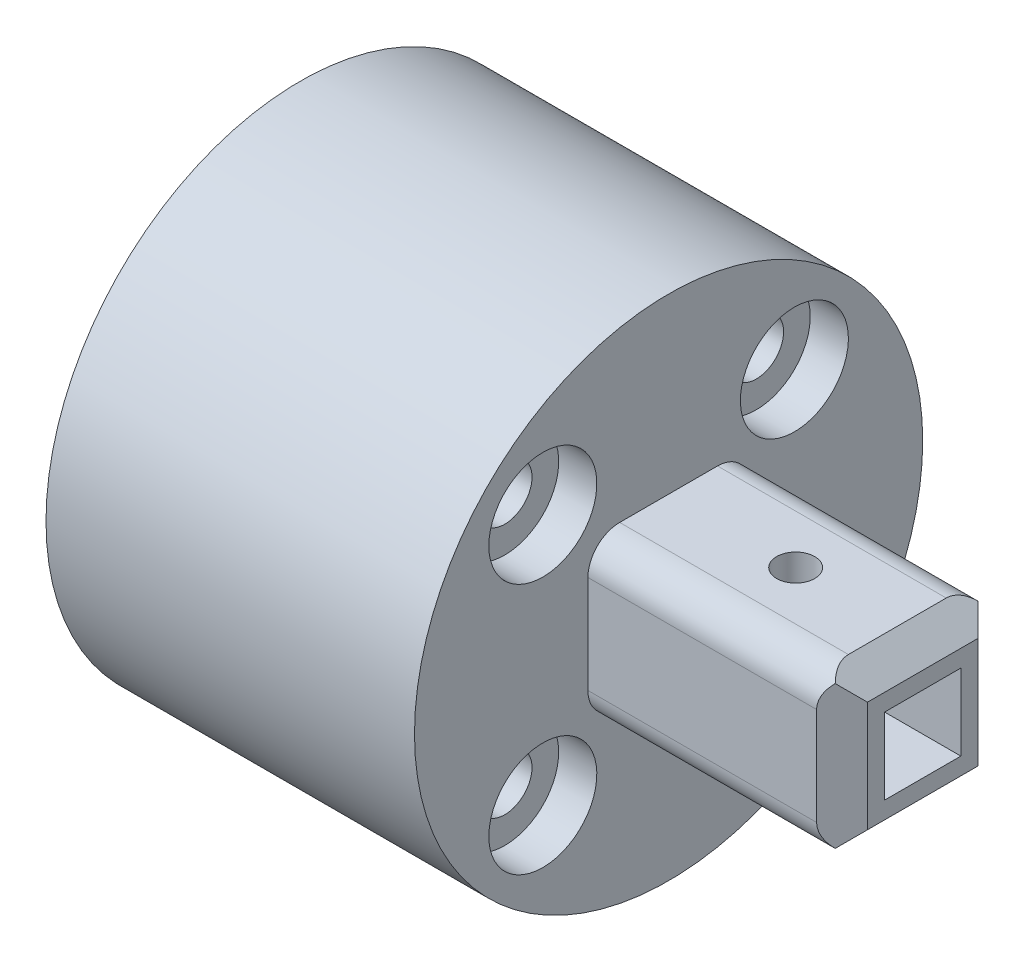
SolidWorks part; units mm, degrees
ref_plane "前视基准面" through (0, 0, 0) normal (0, 0, 1) x (1, 0, 0)
ref_plane "上视基准面" through (0, 0, 0) normal (0, 1, 0) x (1, 0, 0)
ref_plane "右视基准面" through (0, 0, 0) normal (1, 0, 0) x (0, 0, -1)
sketch "草图1" plane through (0, 0, 0) normal (1, 0, 0) x (0, 0, -1)
  circle A0 centre (0, 0) radius 20
  dimension "D1" = 40
extrude "凸台-拉伸1" add sketch "草图1" along normal blind 10
sketch "草图2" plane through (0, 0, 0) normal (-1, 0, 0) x (0, 0, 1)
  line L1 (-7.5, -15.25) -> (7.5, -15.25)
  line L2 (-7.5, -15.25) -> (-7.5, 15.25)
  line L3 (-7.5, 15.25) -> (7.5, 15.25)
  line L4 (7.5, -15.25) -> (7.5, 15.25)
  line L5 (-7.5, -15.25) -> (7.5, 15.25) construction
  line L6 (-7.5, 15.25) -> (7.5, -15.25) construction
  point P0 (0, 0)
  dimension "D1" = 15
  dimension "D2" = 30.5
extrude "切除-拉伸1" cut sketch "草图2" against normal blind 4
sketch "草图3" plane through (4, 0, 0) normal (-1, 0, 0) x (0, 0, 1)
  circle A0 centre (0, 0) radius 8.75
  dimension "D1" = 17.5
extrude "切除-拉伸2" cut sketch "草图3" along normal blind 4
sketch "草图4" plane through (0, 0, 0) normal (-1, 0, 0) x (0, 0, 1)
  line L1 (-9, -16) -> (9, -16)
  line L2 (-9, -16) -> (-9, 16)
  line L3 (-9, 16) -> (9, 16)
  line L4 (9, -16) -> (9, 16)
  line L5 (-9, -16) -> (9, 16) construction
  line L6 (-9, 16) -> (9, -16) construction
  circle A0 centre (0, 0) radius 20
  dimension "D3" = 40
  dimension "D1" = 32
  dimension "D2" = 18
extrude "凸台-拉伸2" add sketch "草图4" along normal blind 19
fillet "圆角1" radius 3 4 edges at (-9.5, -16, -9) (-9.5, -16, 9) (-9.5, 16, -9) (-9.5, 16, 9)
sketch "草图5" plane through (-19, 0, 0) normal (-1, 0, 0) x (0, 0, 1)
  line L0 (-6, -16) -> (6, -16) construction
  line L1 (6, 16) -> (-6, 16) construction
  circle A0 centre (0, -16) radius 2.5
  circle A1 centre (0, 16) radius 2.5
  dimension "D1" = 5
  dimension "D2" = 5
extrude "切除-拉伸3" cut sketch "草图5" against normal blind 20
fillet "圆角2" radius 3 4 edges at (-9.5, -16, -2.5) (-9.5, -16, 2.5) (-9.5, 16, 2.5) (-9.5, 16, -2.5)
sketch "草图6" plane through (10, 0, 0) normal (1, 0, 0) x (0, 0, -1)
  line L0 (0, 0) -> (20, 0) construction
  line L1 (0, 0) -> (18.216, -18.216) construction
  circle A0 centre (0, 0) radius 14 construction
  circle A2 centre (9.8995, -9.8995) radius 2.15
  circle A3 centre (0, 0) radius 14 construction
  circle A4 centre (-9.8995, -9.8995) radius 2.15
  circle A5 centre (0, 0) radius 14 construction
  circle A6 centre (-9.8995, 9.8995) radius 2.15
  circle A7 centre (0, 0) radius 14 construction
  circle A8 centre (9.8995, 9.8995) radius 2.15
  point P21 (0, 0)
  dimension "D1" = 28
  dimension "D3" = 4.3
  dimension "D2" = 45
  dimension "D4" = 4
extrude "切除-拉伸4" cut sketch "草图6" against normal blind 43
fillet "圆角3" radius 1 8 edges at (-9.5, -7.9467, 9) (-9.5, -11.8523, 9) (-9.5, -11.8523, -9) (-9.5, -7.9467, -9) (-9.5, 7.9467, -9) (-9.5, 11.8523, -9) (-9.5, 11.8523, 9) (-9.5, 7.9467, 9)
sketch "草图7" plane through (10, 0, 0) normal (1, 0, 0) x (0, 0, -1)
  circle A0 centre (9.8995, -9.8995) radius 4.25
  dimension "D1" = 8.5
extrude "切除-拉伸5" cut sketch "草图7" against normal blind 3
pattern_circular "阵列(圆周)1" count 4 over 360 about axis through (0, 0, 0) along (1, 0, 0) of "切除-拉伸5"
sketch "草图8" plane through (10, 0, 0) normal (1, 0, 0) x (0, 0, -1)
  line L1 (6.35, -6.35) -> (-6.35, -6.35)
  line L2 (6.35, -6.35) -> (6.35, 6.35)
  line L3 (6.35, 6.35) -> (-6.35, 6.35)
  line L4 (-6.35, -6.35) -> (-6.35, 6.35)
  line L5 (6.35, -6.35) -> (-6.35, 6.35) construction
  line L6 (6.35, 6.35) -> (-6.35, -6.35) construction
  point P0 (0, 0)
  dimension "D1" = 12.7
  dimension "D2" = 12.7
extrude "凸台-拉伸3" add sketch "草图8" along normal blind 20
sketch "草图9" plane through (30, 0, 0) normal (1, 0, 0) x (0, 0, -1)
  line L1 (3, -3) -> (-3, -3)
  line L2 (3, -3) -> (3, 3)
  line L3 (3, 3) -> (-3, 3)
  line L4 (-3, -3) -> (-3, 3)
  line L5 (3, -3) -> (-3, 3) construction
  line L6 (3, 3) -> (-3, -3) construction
  point P0 (0, 0)
  dimension "D1" = 6
  dimension "D2" = 6
extrude "切除-拉伸6" cut sketch "草图9" against normal blind 35
sketch "草图10" plane through (1, 0, 0) normal (-1, 0, 0) x (0, 0, 1)
  line L0 (-3, 3) -> (3, 3) construction
  line L1 (-1.5, 3) -> (1.5, 3)
  line L2 (-1.5, 3) -> (-1.5, 18)
  line L3 (-1.5, 18) -> (1.5, 18)
  line L4 (1.5, 3) -> (1.5, 18)
  arc A0 (2.3848, 15.25) -> (-2.3848, 15.25) centre (0, 16) ccw construction
  dimension "D1" = 3
  dimension "D2" = 1.5
extrude "切除-拉伸7" cut sketch "草图10" against normal blind 5
sketch "草图11" plane through (1, 0, 0) normal (-1, 0, 0) x (0, 0, 1)
  circle A0 centre (0, 16) radius 2.5
  dimension "D1" = 5
extrude "切除-拉伸8" cut sketch "草图11" against normal blind 5
sketch "草图12" plane through (0, -6.35, 0) normal (0, -1, 0) x (1, 0, 0)
  line L0 (10, 6.35) -> (10, -6.35) construction
  line L1 (30, 6.35) -> (10, 6.35) construction
  circle A0 centre (20, 0) radius 1.5
  dimension "D1" = 3
  dimension "D2" = 10
  dimension "D3" = 6.35
extrude "切除-拉伸9" cut sketch "草图12" against normal blind 17
chamfer "倒角1" distance 2 angle 45 4 edges at (30, 0, 6.35) (30, 6.35, 0) (30, 0, -6.35) (30, -6.35, 0)
fillet "圆角4" radius 3 1 edges at (6, 3, 0)
fillet "圆角5" radius 2.5 4 edges at (19, -6.35, -6.35) (19, -6.35, 6.35) (19, 6.35, 6.35) (19, 6.35, -6.35)
